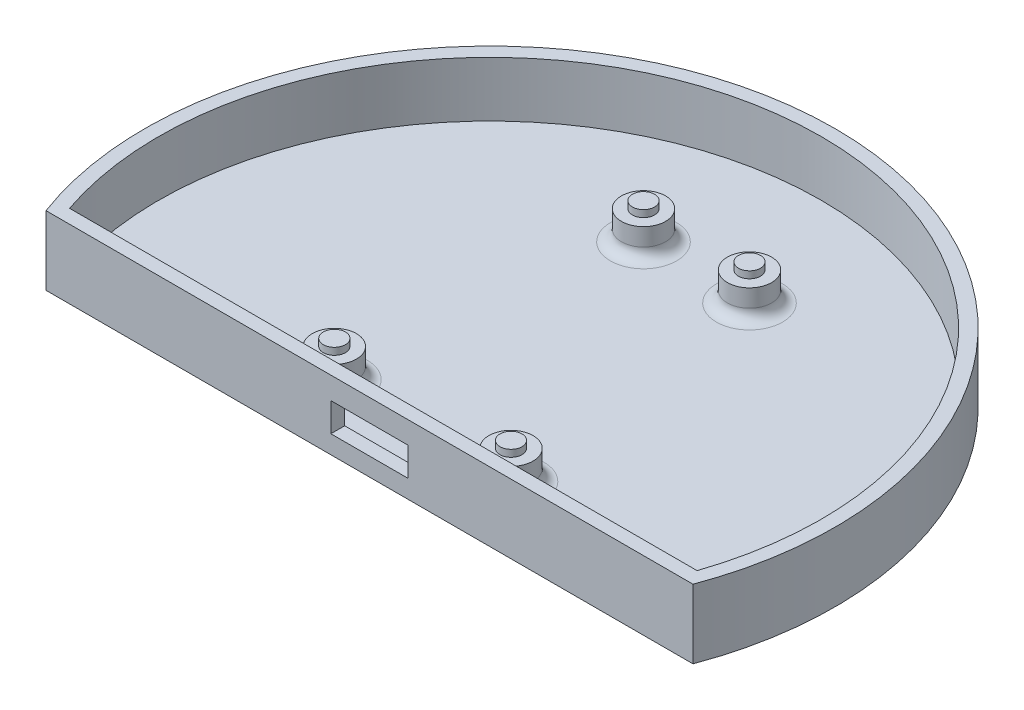
SolidWorks part; units mm, degrees
ref_plane "Front Plane" through (0, 0, 0) normal (0, 0, 1) x (1, 0, 0)
ref_plane "Top Plane" through (0, 0, 0) normal (0, 1, 0) x (1, 0, 0)
ref_plane "Right Plane" through (0, 0, 0) normal (1, 0, 0) x (0, 0, -1)
sketch "Sketch1" plane through (0, 0, 0) normal (0, 1, 0) x (1, 0, 0)
  line L0 (-15.875, 9.1654) -> (0, 0)
  line L1 (-15.875, 9.1654) -> (0, -18.3309)
  line L2 (0, -18.3309) -> (15.875, 9.1654)
  line L3 (15.875, 9.1654) -> (-15.875, 9.1654)
  line L4 (0, 0) -> (-5.9228, 0)
  line L5 (22.1345, 21.6916) -> (35.4695, -1.4053)
  line L6 (-35.4695, -1.4053) -> (-22.1345, 21.6916)
  line L7 (-14.464, -18.3309) -> (-30.3981, -18.3309)
  line L8 (-35.4695, -1.4053) -> (-14.464, -18.3309)
  line L9 (14.464, -18.3309) -> (35.4695, -1.4053)
  line L10 (8.643, 21.6916) -> (22.1345, 21.6916)
  line L11 (-23.107, -3.3607) -> (-8.643, 21.6916)
  line L12 (-8.643, 21.6916) -> (8.643, 21.6916)
  line L13 (0, 0) -> (0, 5.4665) construction
  line L14 (23.107, -3.3607) -> (14.464, -18.3309)
  line L15 (8.643, 21.6916) -> (23.107, -3.3607)
  line L16 (-14.464, -18.3309) -> (-23.107, -3.3607)
  line L17 (14.464, -18.3309) -> (-14.464, -18.3309)
  line L18 (0, 0) -> (0, 16.6878)
  line L19 (0, 0) -> (14.4521, -8.3439)
  line L20 (0, 0) -> (-14.4521, -8.3439)
  line L21 (-8.643, 21.6916) -> (-22.1345, 21.6916)
  line L22 (14.464, -18.3309) -> (30.3981, -18.3309)
  line L23 (-30.3981, -18.3309) -> (-33.817, -18.3309)
  line L24 (30.3981, -18.3309) -> (33.817, -18.3309)
  line L25 (-35.0156, -18.7507) -> (35.0156, -18.7507)
  line L26 (-35.0156, -18.7507) -> (-36.0904, -18.7507)
  line L27 (35.0156, -18.7507) -> (36.0904, -18.7507)
  line L28 (35.0156, -20.3382) -> (37.2102, -20.3382)
  line L29 (-35.0156, -20.3382) -> (-37.2102, -20.3382)
  line L30 (-35.0156, -20.3382) -> (35.0156, -20.3382)
  circle A0 centre (0, 0) radius 9.1654 construction
  circle A1 centre (-6.096, 17.272) radius 1.27
  circle A2 centre (-10.16, -14.224) radius 1.27
  circle A3 centre (10.16, -14.224) radius 1.27
  circle A4 centre (6.096, 17.272) radius 1.27
  arc A5 (35.0156, -18.7507) -> (-35.0156, -18.7507) centre (0, -6.4857) ccw
  arc A6 (33.817, -18.3309) -> (-33.817, -18.3309) centre (0, -6.4857) ccw
  arc A7 (36.0904, -18.7507) -> (-36.0904, -18.7507) centre (0, -6.4857) ccw
  arc A8 (37.2102, -20.3382) -> (-37.2102, -20.3382) centre (0, -6.4857) ccw
  arc A9 (35.9745, -19.0866) -> (-35.9745, -19.0866) centre (0, -6.4857) ccw construction
  point P1 (18.7617, 27.5336)
  point P9 (-18.7617, 27.5336)
  point P17 (0, 21.6916)
  point P23 (0, 0)
  point P26 (0, 0)
  point P28 (0, 0)
  dimension "D16" = 2.54
  dimension "D19" = 2.54
  dimension "D1" = 30
  dimension "D2" = 31.75
  dimension "D3" = 11.684
  dimension "D4" = 26.67
  dimension "D5" = 60
  dimension "D6" = 21.6916
  dimension "D7" = 23.107
  dimension "D8" = 3.3607
  dimension "D9" = 21.6916
  dimension "D10" = 8.643
  dimension "D11" = 18.3309
  dimension "D12" = 1.27
  dimension "D13" = 16.6878
  dimension "D14" = 14.4521
  dimension "D15" = 8.3439
  dimension "D17" = 6.096
  dimension "D18" = 17.272
  dimension "D20" = 10.16
  dimension "D21" = 14.224
  dimension "D22" = 1.016
  dimension "D23" = 26.67
  dimension "D24" = 31.75
  dimension "D25" = 31.75
  dimension "D26" = 15.875
  dimension "D27" = 9.1654
  dimension "D28" = 14.464
  dimension "D29" = 1.5875
extrude "Boss-Extrude1" add sketch "Sketch1" along normal blind 1.5875 contours L20 L0 L1 | L19 L20 L1 L2 | L18 L19 L2 L3 | L0 L18 L3 | L15 L12 L11 L3 A1 A4 | L17 L14 L15 L2 A3 | A3 | A2 | L17 L1 L11 L16 A2 | A1 | A4 | L10 L15 L14 L9 L5 | L24 A6 L9 L22 | L5 A6 | L10 A6 L21 L12 | L11 L21 L6 L8 L16 | L8 A6 L23 L7 | L6 A6 | L25 A5 A6 L24 L22 L17 L7 L23 | L27 A7 L26 A5 | L28 A8 L29 L30 A7 L27 L25 L26 region at (-5.2917, 0, -6.1103) region at (-7.9375, 0, -1.5276) region at (-11.9634, 0, -15.2579) region at (-12.873, 0, 7.292) region at (-22.682, 0, -6.0805) region at (6.6146, 0, -3.8189) region at (0, 0, 7.6379) region at (0, 0, -24.7832) region at (12.873, 0, 7.292) region at (22.682, 0, -6.0805) region at (-28.3902, 0, 12.5045) region at (-29.6964, 0, -10.6595) region at (28.3902, 0, 12.5045) region at (29.6964, 0, -10.6595) region at (0, 0, -29.7246) region at (-35.553, 0, 17.8369) region at (0, 0, 19.3804) region at (-6.096, 0, -17.272) region at (-10.16, 0, 14.224) region at (10.16, 0, 14.224) region at (6.096, 0, -17.272)
sketch "Sketch2" plane through (0, 1.5875, 0) normal (0, 1, 0) x (1, 0, 0)
  line L0 (37.2102, -20.3382) -> (-37.2102, -20.3382)
  line L1 (36.0904, -18.7507) -> (-36.0904, -18.7507)
  line L3 (37.2102, -18.7507) -> (-37.2102, -18.7507) construction
  circle A0 centre (0, -6.4857) radius 35.8315
  circle A1 centre (0, -6.4857) radius 39.705
  arc A2 (-35.5113, -20.3382) -> (35.5113, -20.3382) centre (0, -6.4857) ccw
  arc A3 (36.0904, -18.7507) -> (-36.0904, -18.7507) centre (0, -6.4857) ccw
  circle A4 centre (0, -6.4857) radius 38.1175 construction
  point P16 (38.1175, -6.4857)
  line M1 (-37.2102, -20.3382) -> (37.2102, -20.3382)
  arc M2 (37.2102, -20.3382) -> (-37.2102, -20.3382) centre (0, -6.4857) ccw
  dimension "D1" = 3.8735
  dimension "D2" = 1.5875
  dimension "D3" = 1.5875
extrude "Boss-Extrude2" add sketch "Sketch2" along normal blind 6.35 contours A3 L1 A0 L0 M1 M2 | L0 A0 L1 region at (36.3608, 1.5875, 19.3804) region at (0, 1.5875, 19.542)
sketch "Sketch5" plane through (0, 1.5875, 0) normal (0, 1, 0) x (1, 0, 0)
  circle A0 centre (-6.096, 17.272) radius 2.54
  circle A1 centre (6.096, 17.272) radius 2.54
  circle A2 centre (10.16, -14.224) radius 2.54
  circle A3 centre (-10.16, -14.224) radius 2.54
  dimension "D1" = 5.08
  dimension "D2" = 5.08
  dimension "D3" = 5.08
  dimension "D4" = 5.08
extrude "Boss-Extrude3" add sketch "Sketch5" along normal blind 3.302
sketch "Sketch6" plane through (0, 4.8895, 0) normal (0, 1, 0) x (1, 0, 0)
  circle A0 centre (-6.096, 17.272) radius 1.27
  circle A1 centre (6.096, 17.272) radius 1.27
  circle A2 centre (10.16, -14.224) radius 1.27
  circle A3 centre (-10.16, -14.224) radius 1.27
extrude "Boss-Extrude4" add sketch "Sketch6" along normal blind 0.8
fillet "Fillet1" radius 1.27 4 edges at (-10.16, 1.5875, 16.764) (10.16, 1.5875, 16.764) (6.096, 1.5875, -14.732) (-6.096, 1.5875, -14.732)
sketch "Sketch8" plane through (0, 0, 20.3382) normal (0, 0, 1) x (1, 0, 0)
  line L0 (0, 7.9375) -> (0, 0)
  line L1 (-37.2102, 7.9375) -> (37.2102, 7.9375) construction
  line L2 (-4.445, 5.3975) -> (-4.445, 2.0955)
  line L3 (4.445, 5.3975) -> (4.445, 2.0955)
  line L4 (-4.445, 5.3975) -> (4.445, 5.3975)
  line L5 (39.705, 0) -> (-39.705, 0) construction
  line L6 (-4.445, 2.0955) -> (4.445, 2.0955)
  line L8 (-4.445, 7.9375) -> (-4.445, 0) construction
  line L9 (4.445, 7.9375) -> (4.445, 0) construction
  dimension "D3" = 5.3975
  dimension "D1" = 4.445
  dimension "D2" = 4.445
  dimension "D4" = 3.302
extrude "Cut-Extrude2" cut sketch "Sketch8" against normal blind 1.5875 contours L2 L6 L0 L4 | L0 L6 L3 L4 region at (2.2225, 3.7465, 20.3382) region at (-2.2225, 3.7465, 20.3382)
